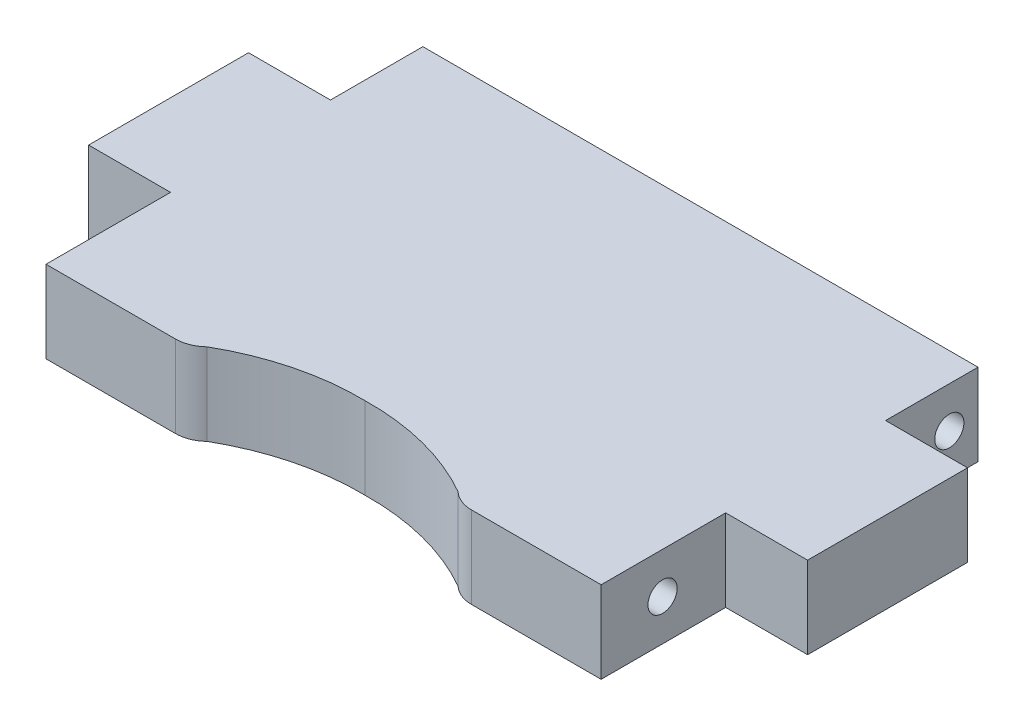
SolidWorks part; units mm, degrees
ref_plane "Front Plane" through (0, 0, 0) normal (0, 0, 1) x (1, 0, 0)
ref_plane "Top Plane" through (0, 0, 0) normal (0, 1, 0) x (1, 0, 0)
ref_plane "Right Plane" through (0, 0, 0) normal (1, 0, 0) x (0, 0, -1)
sketch "Sketch1" plane through (0, 0, 0) normal (0, 1, 0) x (1, 0, 0)
  line L0 (0, -0.0254) -> (0, 0.0372) construction
  line L1 (-21.5138, -15.875) -> (-9.73, -15.875)
  line L2 (-21.5138, -15.875) -> (-21.5138, -6.223)
  line L3 (-0.0503, 0.0373) -> (21.5138, -15.875) construction
  line L4 (21.5138, 13.335) -> (-21.5138, 13.335) construction
  line L5 (-21.5138, -15.875) -> (12.9943, 9.5885) construction
  line L6 (0, 0.0372) -> (0, -30.5404) construction
  line L7 (21.5138, 13.335) -> (21.5138, 6.1722)
  line L8 (0, -0.0254) -> (6.6747, -0.0254) construction
  line L9 (21.5138, -6.223) -> (21.5138, -15.875)
  line L10 (21.5138, 6.1722) -> (27.8638, 6.1722)
  line L11 (21.5138, 12.6365) -> (8.8138, 12.6365) construction
  line L12 (21.5138, -6.223) -> (27.8638, -6.223)
  line L13 (27.8638, 6.1722) -> (27.8638, -6.223)
  line L14 (8.8138, 12.6365) -> (8.8138, 9.5885) construction
  line L15 (8.8138, 9.5885) -> (21.5138, 9.5885) construction
  line L16 (0, -0.0254) -> (53.5858, -0.0254) construction
  line L17 (8.7571, -12.6016) -> (8.7708, -9.5536) construction
  line L18 (21.457, -12.6586) -> (8.7571, -12.6016) construction
  line L19 (8.7708, -9.5536) -> (21.4707, -9.6107) construction
  line L20 (-21.5138, -6.223) -> (-27.8638, -6.223)
  line L21 (-27.8638, 6.1722) -> (-27.8638, -6.223)
  line L22 (-21.5138, 6.1722) -> (-27.8638, 6.1722)
  line L23 (-21.5138, 13.335) -> (-21.5138, 6.1722)
  line L24 (-21.5138, 13.335) -> (21.5138, 13.335)
  line L25 (-9.73, -15.1768) -> (-9.73, -15.875)
  line L26 (9.73, -15.875) -> (21.5138, -15.875)
  line L27 (9.73, -15.1768) -> (9.73, -15.875)
  arc A0 (0, -12.6684) -> (-9.73, -15.1768) centre (-0.3269, -31.5257) ccw
  arc A1 (0, -12.6684) -> (9.73, -15.1768) centre (0.3269, -31.5257) cw
  point P0 (0, 0)
  dimension "D1" = 6.1976
  dimension "D4" = 12.3952
  dimension "D6" = 6.35
  dimension "D7" = 3.048
  dimension "D8" = 12.7
extrude "Boss-Extrude1" add sketch "Sketch1" along normal blind 6.35
sketch "Sketch2" plane through (-21.5138, 0, 0) normal (-1, 0, 0) x (0, 0, 1)
  line L6 (0, 0) -> (0, 5.0918) construction
  circle A0 centre (-11.1125, 3.175) radius 1.1303
  circle A1 centre (11.1125, 3.175) radius 1.1303
  dimension "D1" = 2.2606
extrude "Cut-Extrude1" cut sketch "Sketch2" against normal blind 12.7
mirror "Mirror1" about plane through (0, 0, 0) normal (1, 0, 0) of "Cut-Extrude1"
fillet "Fillet1" radius 2.54 2 edges at (9.73, 3.175, 15.875) (-9.73, 3.175, 15.875)
